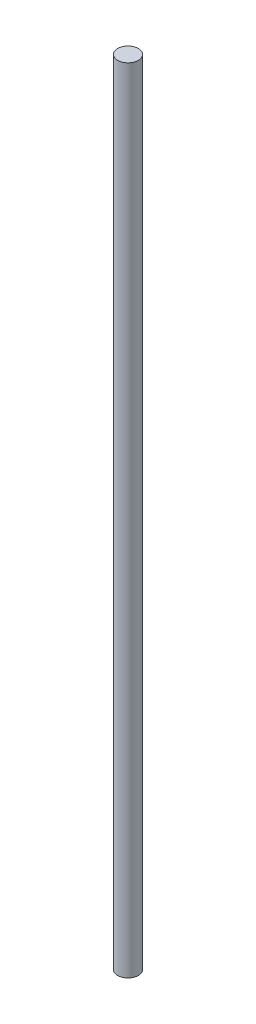
SolidWorks part; units mm, degrees
ref_plane "Front Plane" through (0, 0, 0) normal (0, 0, 1) x (1, 0, 0)
ref_plane "Top Plane" through (0, 0, 0) normal (0, 1, 0) x (1, 0, 0)
ref_plane "Right Plane" through (0, 0, 0) normal (1, 0, 0) x (0, 0, -1)
sketch "Sketch1" plane through (0, 0, 0) normal (0, 1, 0) x (1, 0, 0)
  circle A0 centre (0, 0) radius 7.9375
  dimension "D1" = 15.875
extrude "Boss-Extrude1" add sketch "Sketch1" along normal mid plane 609.6
